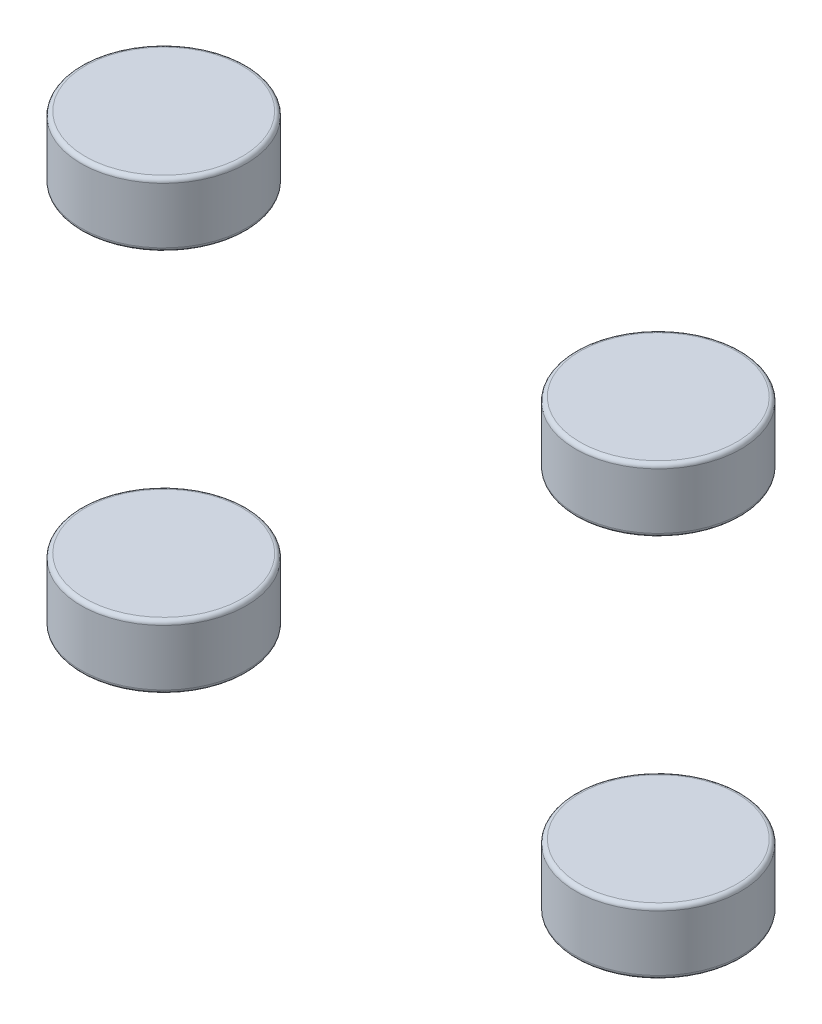
SolidWorks part; units mm, degrees
ref_plane "Front Plane" through (0, 0, 0) normal (0, 0, 1) x (1, 0, 0)
ref_plane "Top Plane" through (0, 0, 0) normal (0, 1, 0) x (1, 0, 0)
ref_plane "Right Plane" through (0, 0, 0) normal (1, 0, 0) x (0, 0, -1)
sketch3d "Left Suspension"
  line L0 (1180, -220, 108.03) -> (1122, -574, 138)
  line L1 (1122, -574, 138) -> (1020, -220, 136.03)
  line L2 (1020, -220, 136.03) -> (1180, -220, 108.03)
  line L3 (1030, -233, 255) -> (1170, -233, 242)
  line L4 (1170, -233, 242) -> (1150, -567.5, 313)
  line L5 (1150, -567.5, 313) -> (1030, -233, 255)
  line L6 (1165, -550.5, 318) -> (1165, -245, 393)
  line L7 (1165, -245, 393) -> (1165, -215, 393)
  line L8 (1165, -215, 393) -> (1165, -75, 333)
  line L9 (1165, -245, 393) -> (1155, -230, 333)
  line L10 (1155, -230, 333) -> (1175, -230, 333)
  line L11 (1175, -230, 333) -> (1165, -245, 393)
  line L12 (1165, -215, 393) -> (1155, -230, 333)
  line L13 (1165, -215, 393) -> (1175, -230, 333)
  line L14 (1244, -554, 222) -> (1251, -246, 222)
  line L15 (1130, -535, 233) -> (1244, -554, 222)
  line L16 (1130, -600, 235) -> (1130, -535, 233)
  line L34 (-420, -600, 235) -> (-420, -543.5, 233)
  line L35 (-420, -543.5, 233) -> (-412.5, -542, 156)
  line L36 (-490, -587, 155) -> (-491, -160, 151)
  line L37 (-412.5, -352, 446) -> (-446, -255, 425)
  line L38 (-380, -255, 425) -> (-412.5, -383, 405)
  line L39 (-446, -255, 425) -> (-412.5, -383, 405)
  line L40 (-380, -255, 425) -> (-446, -255, 425)
  line L41 (-412.5, -352, 446) -> (-380, -255, 425)
  line L42 (-412.5, -352, 446) -> (-412.5, -210.5, 587.5)
  line L43 (-412.5, -383, 405) -> (-412.5, -352, 446)
  line L44 (-412.5, -542, 156) -> (-412.5, -383, 405)
  line L45 (-578, -235, 280) -> (-416, -556, 332)
  line L46 (-270, -235, 280) -> (-578, -235, 280)
  line L47 (-416, -556, 332) -> (-270, -235, 280)
  line L48 (-427.5, -581, 127) -> (-236, -150, 142)
  line L49 (-536.5, -150, 117) -> (-427.5, -581, 127)
  line L50 (-236, -150, 142) -> (-536.5, -150, 117)
  point P1 (1180, -220, 108.03)
  point P2 (1122, -574, 138)
  point P11 (1170, -233, 242)
sketch3d "3D Sketch 1"
  circle A0 centre (-420, -600, 235) radius 259
  circle A1 centre (1130, -600, 235) radius 259
  point P2 (-420, -341, 235)
  point P6 (1130, -341, 235)
  point P9 (1130, -600, 235)
  dimension "D1" = 518
  dimension "D2" = 518
extrude "Left Wheels" add sketch "3D Sketch 1" along direction (0, 1, 0) on the side against the normal blind 100.5 and the other way blind 100.5
fillet "Fillet1" radius 13 2 edges at (1130, -700.5, 494) (1130, -499.5, 494)
fillet "Fillet2" radius 13 2 edges at (-420, -700.5, 494) (-420, -499.5, 494)
sketch3d "Right sus"
  line L1 (1175, -230, 333) -> (1165, -245, 393) construction
  line L2 (1165, -215, 393) -> (1175, -230, 333) construction
  line L3 (1165, -245, 393) -> (1155, -230, 333) construction
  line L4 (1165, -215, 393) -> (1155, -230, 333) construction
  line L5 (1165, -215, 393) -> (1165, -75, 333) construction
  line L7 (1165, -550.5, 318) -> (1165, -245, 393) construction
  line L8 (1244, -554, 222) -> (1251, -246, 222) construction
  line L10 (1130, -600, 235) -> (1130, -535, 233) construction
  line L12 (-446, -255, 425) -> (-412.5, -383, 405) construction
  line L13 (-380, -255, 425) -> (-446, -255, 425) construction
  line L14 (-412.5, -352, 446) -> (-380, -255, 425) construction
  line L15 (-412.5, -352, 446) -> (-412.5, -210.5, 587.5) construction
  line L17 (-490, -587, 155) -> (-491, -160, 151) construction
  line L18 (-420, -600, 235) -> (-420, -543.5, 233) construction
  line L20 (-412.5, -542, 156) -> (-412.5, -383, 405) construction
  line L21 (-380, -255, 425) -> (-412.5, -383, 405) construction
  line L23 (1170, -233, 242) -> (1150, -567.5, 313) construction
  line L24 (1150, -567.5, 313) -> (1030, -233, 255) construction
  line L26 (1122, -574, 138) -> (1020, -220, 136.03) construction
  line L27 (1020, -220, 136.03) -> (1180, -220, 108.03) construction
  line L29 (-236, -150, 142) -> (-536.5, -150, 117) construction
  line L30 (-536.5, -150, 117) -> (-427.5, -581, 127) construction
  line L32 (-416, -556, 332) -> (-270, -235, 280) construction
  line L33 (-270, -235, 280) -> (-578, -235, 280) construction
  line L68 (-270, 235, 280) -> (-578, 235, 280)
  line L69 (-416, 556, 332) -> (-270, 235, 280)
  line L70 (-578, 235, 280) -> (-416, 556, 332)
  line L71 (-536.5, 150, 117) -> (-427.5, 581, 127)
  line L72 (-236, 150, 142) -> (-536.5, 150, 117)
  line L73 (-427.5, 581, 127) -> (-236, 150, 142)
  line L74 (1020, 220, 136.03) -> (1180, 220, 108.03)
  line L75 (1122, 574, 138) -> (1020, 220, 136.03)
  line L76 (1180, 220, 108.03) -> (1122, 574, 138)
  line L77 (1150, 567.5, 313) -> (1030, 233, 255)
  line L78 (1170, 233, 242) -> (1150, 567.5, 313)
  line L79 (1030, 233, 255) -> (1170, 233, 242)
  line L80 (-380, 255, 425) -> (-412.5, 383, 405)
  line L81 (-412.5, 542, 156) -> (-412.5, 383, 405)
  line L82 (-420, 543.5, 233) -> (-412.5, 542, 156)
  line L83 (-420, 600, 235) -> (-420, 543.5, 233)
  line L84 (-490, 587, 155) -> (-491, 160, 151)
  line L85 (-412.5, 383, 405) -> (-412.5, 352, 446)
  line L86 (-412.5, 352, 446) -> (-412.5, 210.5, 587.5)
  line L87 (-412.5, 352, 446) -> (-380, 255, 425)
  line L88 (-380, 255, 425) -> (-446, 255, 425)
  line L89 (-446, 255, 425) -> (-412.5, 383, 405)
  line L90 (-412.5, 352, 446) -> (-446, 255, 425)
  line L91 (1130, 600, 235) -> (1130, 535, 233)
  line L92 (1130, 535, 233) -> (1244, 554, 222)
  line L93 (1244, 554, 222) -> (1251, 246, 222)
  line L94 (1165, 550.5, 318) -> (1165, 245, 393)
  line L95 (1165, 245, 393) -> (1165, 215, 393)
  line L96 (1165, 215, 393) -> (1165, 75, 333)
  line L97 (1165, 215, 393) -> (1155, 230, 333)
  line L98 (1165, 245, 393) -> (1155, 230, 333)
  line L99 (1165, 215, 393) -> (1175, 230, 333)
  line L100 (1175, 230, 333) -> (1165, 245, 393)
  line L101 (1155, 230, 333) -> (1175, 230, 333)
sketch3d "3DSketch3"
  circle A0 centre (1130, 600, 235) radius 259
  circle A1 centre (-420, 600, 235) radius 259
  point P2 (1130, 859, 235)
  point P6 (-420, 859, 235)
  dimension "D1" = 518
  dimension "D2" = 518
extrude "Right Wheels" add sketch "3DSketch3" along direction (0, 1, 0) on the side of the normal blind 100.5 and the other way blind 100.5 separate body
fillet "Fillet4" radius 13 2 edges at (-420, 499.5, 494) (-420, 700.5, 494)
fillet "Fillet3" radius 13 2 edges at (1130, 499.5, 494) (1130, 700.5, 494)
ref_plane "Plane1" through (-936, 0, 0) normal (1, 0, 0) x (0, 0, -1)
ref_plane "Ground" [suppressed] through (0, 0, -24) normal (0, 0, -1) x (-1, 0, 0)
sketch3d "3DSketch4"
  line L0 (0, 0, 0) -> (-807.2705, 0, 0)
  line L1 (-807.2705, 0, 0) -> (-807.2705, 0, 348.5334)
ref_plane "Plane3" through (0, 0, 0) normal (0, 1, 0) x (1, 0, 0)
